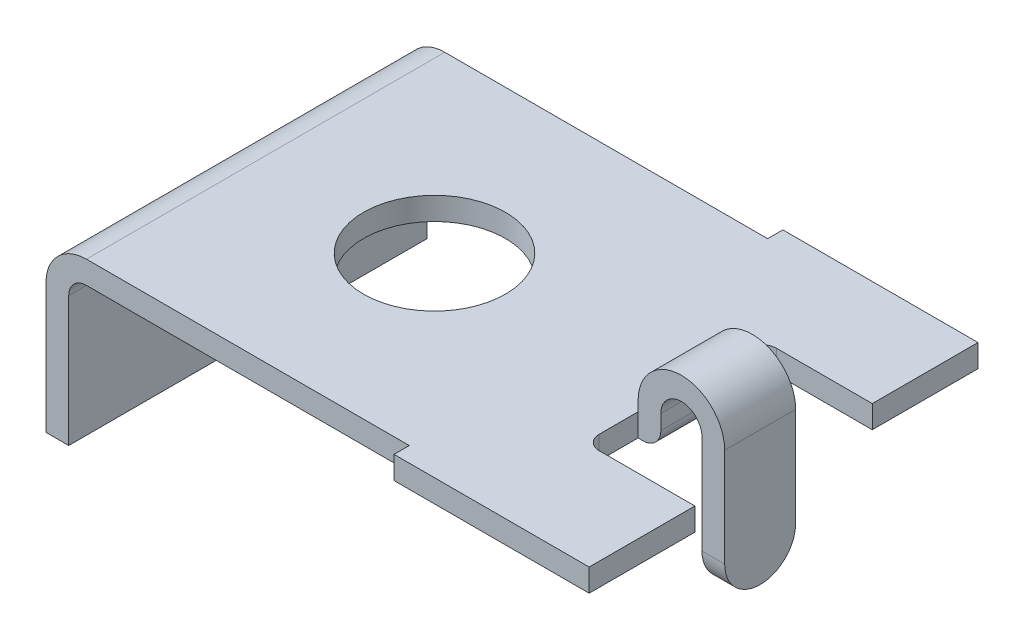
SolidWorks part; units mm, degrees
material "Chrome Stainless Steel"
ref_plane "Front Plane" through (0, 0, 0) normal (0, 0, 1) x (1, 0, 0)
ref_plane "Top Plane" through (0, 0, 0) normal (0, 1, 0) x (1, 0, 0)
ref_plane "Right Plane" through (0, 0, 0) normal (1, 0, 0) x (0, 0, -1)
ref_axis "X-axis" through (-88.99, 0, 0) along (1, 0, 0)
ref_axis "Y-axis" through (0, -55, 0) along (0, 1, 0)
ref_axis "Z-axis" through (0, 0, 55) along (0, 0, -1)
sketch "Sketch1" plane through (0, 0, 0) normal (0, 0, 1) x (1, 0, 0)
  line L0 (0, 0) -> (0, 6.096)
  line L1 (0, 6.096) -> (19.9898, 6.096)
  dimension "D1" = 19.9898
  dimension "D2" = 6.096
extrude "Extrude-Thin1" add sketch "Sketch1" along normal mid plane 12.827 thin thin type one direction wall 0.8128
sketch "Sketch2" plane through (0, 0, 0) normal (0, 0, 1) x (1, 0, 0)
  line L0 (1.4478, 5.2832) -> (19.9898, 5.2832) construction
  line L1 (19.9898, 6.096) -> (13.0048, 6.096)
  line L2 (19.9898, 6.096) -> (19.9898, 5.2832)
  line L3 (19.9898, 5.2832) -> (13.0048, 5.2832)
  line L4 (13.0048, 6.096) -> (13.0048, 5.2832)
  dimension "D1" = 6.985
extrude "Boss-Extrude1" add sketch "Sketch2" along normal mid plane 13.9192
sketch "Sketch3" plane through (0, 6.096, 0) normal (0, 1, 0) x (1, 0, 0)
  line L0 (19.9898, -6.9596) -> (19.9898, 6.9596) construction
  line L1 (19.9898, -3.175) -> (16.0528, -3.175)
  line L2 (19.9898, -3.175) -> (19.9898, 3.175)
  line L3 (19.9898, 3.175) -> (16.0528, 3.175)
  line L4 (16.0528, -3.175) -> (16.0528, 3.175)
  point P6 (16.0528, 0)
  point P7 (19.9898, 0)
  point P8 (19.9898, 0)
  dimension "D1" = 6.35
  dimension "D2" = 3.937
extrude "Cut-Extrude1" cut sketch "Sketch3" against normal through all
sketch "Sketch4" plane through (0, 0, 0) normal (0, 0, 1) x (1, 0, 0)
  line L0 (16.0528, 5.2832) -> (16.0528, 6.4516)
  line L1 (19.1516, 6.4516) -> (19.1516, 1.651)
  line L2 (19.9898, 6.096) -> (13.0048, 6.096) construction
  arc A0 (16.0528, 6.4516) -> (19.1516, 6.4516) centre (17.6022, 6.4516) cw
  point P8 (17.6022, 8.001)
  dimension "D1" = 3.0988
  dimension "D2" = 1.905
  dimension "D3" = 6.35
extrude "Extrude-Thin2" add sketch "Sketch4" along normal mid plane 2.54 thin thin type one direction wall 0.8128
fillet "Fillet1" 2 edges at (18.7452, 1.651, 1.27) (18.7452, 1.651, -1.27) type full round first side face at (17.43, 5.3396, 1.27) second side face at (17.43, 5.3396, -1.27) middle face at (18.7452, 1.651, 0)
fillet "Fillet2" radius 0.635 1 edges at (16.8656, 5.2832, 0)
sketch "Sketch5" plane through (0, 6.096, 0) normal (0, 1, 0) x (1, 0, 0)
  line L0 (0, -6.4135) -> (0, 6.4135) construction
  circle A0 centre (7.493, 0) radius 2.54
  point P5 (0, 0)
  dimension "D1" = 5.08
  dimension "D2" = 4.953
extrude "Cut-Extrude2" cut sketch "Sketch5" against normal through all
fillet "Fillet3" radius 0.508 2 edges at (16.0528, 5.6896, 3.175) (16.0528, 5.6896, -3.175)
